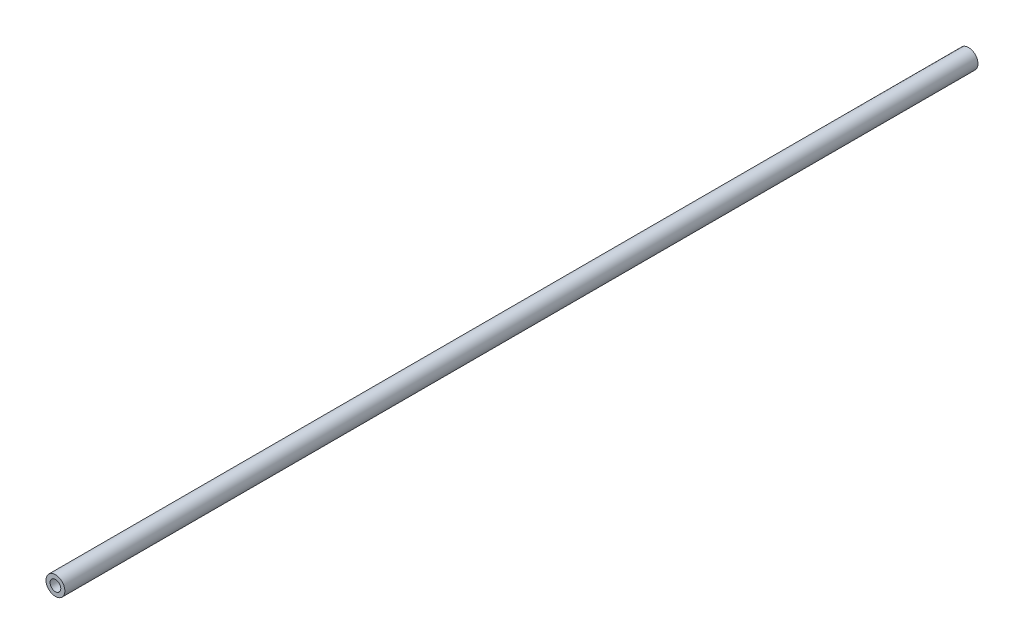
SolidWorks part; units mm, degrees
ref_plane "Front Plane" through (0, 0, 0) normal (0, 0, 1) x (1, 0, 0)
ref_plane "Top Plane" through (0, 0, 0) normal (0, 1, 0) x (1, 0, 0)
ref_plane "Right Plane" through (0, 0, 0) normal (1, 0, 0) x (0, 0, -1)
sketch "Sketch1" plane through (0, 0, 0) normal (0, 0, 1) x (1, 0, 0)
  circle A0 centre (0, 0) radius 3.4
  circle A1 centre (0, 0) radius 6
  dimension "D1" = 12
  dimension "D2" = 6.8
extrude "Boss-Extrude1" add sketch "Sketch1" along normal blind 580
ref_point "Point1"
ref_axis "Axis1" through (0, 0, 519.1711) along (0, 0, -1)
